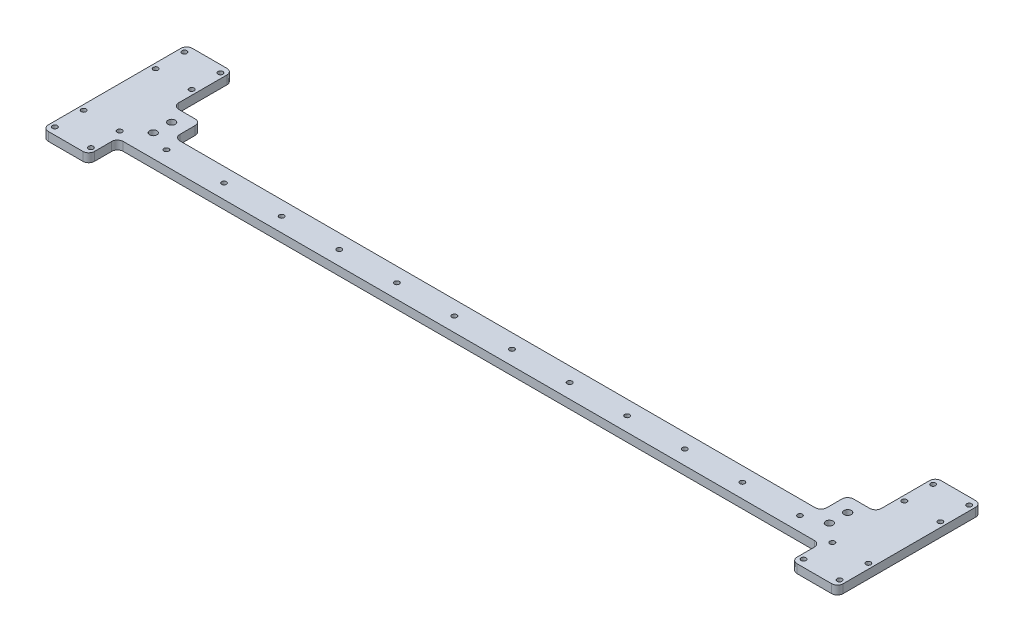
SolidWorks part; units mm, degrees
ref_plane "Front Plane" through (0, 0, 0) normal (0, 0, 1) x (1, 0, 0)
ref_plane "Top Plane" through (0, 0, 0) normal (0, 1, 0) x (1, 0, 0)
ref_plane "Right Plane" through (0, 0, 0) normal (1, 0, 0) x (0, 0, -1)
sketch "Sketch1" plane through (0, 0, 0) normal (0, 1, 0) x (1, 0, 0)
  line L1 (0, 0) -> (552, 0)
  line L2 (0, 0) -> (0, 20)
  line L3 (0, 20) -> (552, 20)
  line L4 (552, 0) -> (552, 20)
  dimension "D1" = 20
  dimension "D2" = 552
extrude "Boss-Extrude1" add sketch "Sketch1" along normal blind 6
ref_plane "Plane1" through (276, 0, 0) normal (1, 0, 0) x (0, 0, -1)
sketch "Sketch3" plane through (0, 0, 0) normal (0, -1, 0) x (1, 0, 0)
  line L0 (0, 0) -> (552, 0) construction
  line L1 (0, -80) -> (32, -80)
  line L2 (0, -80) -> (0, 20)
  line L3 (0, 20) -> (32, 20)
  line L4 (32, -80) -> (32, 20)
  dimension "D1" = 32
  dimension "D2" = 100
  dimension "D3" = 20
extrude "Boss-Extrude2" add sketch "Sketch3" against normal up to surface (6 mm away) up to face at (276, 6, -10)
sketch "Sketch4" plane through (0, 6, 0) normal (0, 1, 0) x (1, 0, 0)
  line L0 (16, -20) -> (16, 80)
  line L1 (0, -20) -> (32, -20) construction
  line L2 (32, 80) -> (0, 80) construction
  line L4 (3.5, -15) -> (28.5, -15)
  line L5 (3.5, -15) -> (3.5, 5)
  line L6 (3.5, 5) -> (28.5, 5)
  line L7 (28.5, -15) -> (28.5, 5)
  line L8 (3.5, -15) -> (28.5, 5) construction
  line L9 (3.5, 5) -> (28.5, -15) construction
  line L10 (3.5, 55) -> (28.5, 55)
  line L11 (3.5, 55) -> (3.5, 75)
  line L12 (3.5, 75) -> (28.5, 75)
  line L13 (28.5, 55) -> (28.5, 75)
  line L14 (3.5, 55) -> (28.5, 75) construction
  line L15 (3.5, 75) -> (28.5, 55) construction
  point P6 (16, -5)
  point P11 (16, 65)
  dimension "D1" = 20
  dimension "D2" = 25
  dimension "D3" = 5
  dimension "D4" = 5
sketch "Sketch7" plane through (0, 6, 0) normal (0, 1, 0) x (1, 0, 0)
  line L0 (276, 0) -> (276, 20) construction
  line L1 (32, 0) -> (552, 0) construction
  line L2 (552, 20) -> (32, 20) construction
  line L3 (276, -3.3) -> (276, 3.3) construction
  line L4 (276, 10) -> (256, 10) construction
  point P11 (256, 10)
  point P13 (216, 10)
  point P14 (176, 10)
  point P15 (136, 10)
  point P16 (96, 10)
  point P17 (56, 10)
  dimension "D1" = 20
  dimension "D3" = 40
  dimension "D2" = 6
hole_wizard "M3 Clearance Hole1" positions "Sketch5" profile "Sketch6" hole size "M3" standard "ANSI Metric" end condition through all
sketch "Sketch5" plane through (0, 6, 0) normal (0, 1, 0) x (1, 0, 0)
  point P0 (3.5, -15)
  point P3 (3.5, 5)
  point P6 (28.5, 5)
  point P9 (28.5, -15)
  point P12 (3.5, 75)
  point P15 (28.5, 75)
  point P18 (28.5, 55)
  point P21 (3.5, 55)
  point P25 (56, 10)
  point P28 (96, 10)
  point P31 (136, 10)
  point P34 (176, 10)
  point P37 (216, 10)
  point P40 (256, 10)
sketch "Sketch6" plane through (3.5, 6, 15) normal (1, 0, 0) x (0, 0, 1)
  line L0 (0, 0) -> (0, 6)
  line L1 (0, 6) -> (1.7, 6)
  line L2 (1.7, 6) -> (1.7, 0)
  line L5 (1.7, 0) -> (0, 0)
  line L11 (0, -6.35) -> (0, 107.95) construction
  dimension "Thru Hole Dia." = 3.4
  dimension "Thru Hole Depth" = 6
sketch "Sketch8" plane through (0, 6, 0) normal (0, 1, 0) x (1, 0, 0)
  line L0 (56.3721, 22) -> (87.6482, 22) construction
  line L1 (552, 20) -> (32, 20) construction
  line L2 (105.1095, -2) -> (88.5975, -2) construction
  line L3 (32, 0) -> (552, 0) construction
  line L4 (34.8662, 80) -> (34.8662, 28.3662) construction
  line L5 (34.8662, -20) -> (34.8662, -8.3662) construction
  line L6 (28.5, -20) -> (28.5, 80) construction
  line L7 (0, -20) -> (32, -20) construction
  line L8 (32, 80) -> (0, 80) construction
  line L9 (28.5, 55) -> (28.5, 75) construction
  circle A0 centre (41.2324, 28.3662) radius 6.3662
  circle A1 centre (28.5, 80) radius 6.3662
  circle A2 centre (28.5, -20) radius 6.3662
  circle A3 centre (41.2324, -8.3662) radius 6.3662
  circle A4 centre (41.2324, 28.3662) radius 10.16
  circle A5 centre (41.2324, -8.3662) radius 10.16
  circle A6 centre (28.5, -20) radius 10.16
  circle A7 centre (28.5, 80) radius 10.16
  dimension "D3" = 12.7324
  dimension "D4" = 20.32
  dimension "D1" = 2
  dimension "D2" = 2
sketch "Sketch10" plane through (0, 6, 0) normal (0, 1, 0) x (1, 0, 0)
  line L5 (32, 20) -> (51.3924, 20)
  line L6 (32, 20) -> (32, 38.5262)
  line L7 (32, 38.5262) -> (51.3924, 38.5262)
  line L8 (51.3924, 20) -> (51.3924, 38.5262)
  circle A2 centre (41.2324, 28.3662) radius 2.525
  point P0 (41.2324, 28.3662)
  dimension "D1" = 5.05
  dimension "D2" = 18.5262
  dimension "D3" = 19.3924
extrude "Boss-Extrude3" add sketch "Sketch10" against normal up to surface (6 mm away) up to face at (3.5, 0, 16.7)
sketch "Sketch12" plane through (0, 6, 0) normal (0, 1, 0) x (1, 0, 0)
  line L0 (41.2324, 28.3662) -> (41.2324, 15.6362) construction
  circle A0 centre (41.2324, 15.6362) radius 2.525
  circle A2 centre (41.2324, 28.3662) radius 2.525 construction
  dimension "D1" = 12.73
extrude "Cut-Extrude2" cut sketch "Sketch12" against normal through all
fillet "Fillet2" radius 4 8 edges at (32, 3, 20) (0, 3, 20) (0, 3, -80) (32, 3, -80) (32, 3, -38.5262) (51.3924, 3, -38.5262) (51.3924, 3, -20) (32, 3, 0)
mirror "Mirror1" about plane through (276, 0, 0) normal (1, 0, 0) of "Cut-Extrude2", "Boss-Extrude2", "M3 Clearance Hole1", "Boss-Extrude3", "Fillet2"
